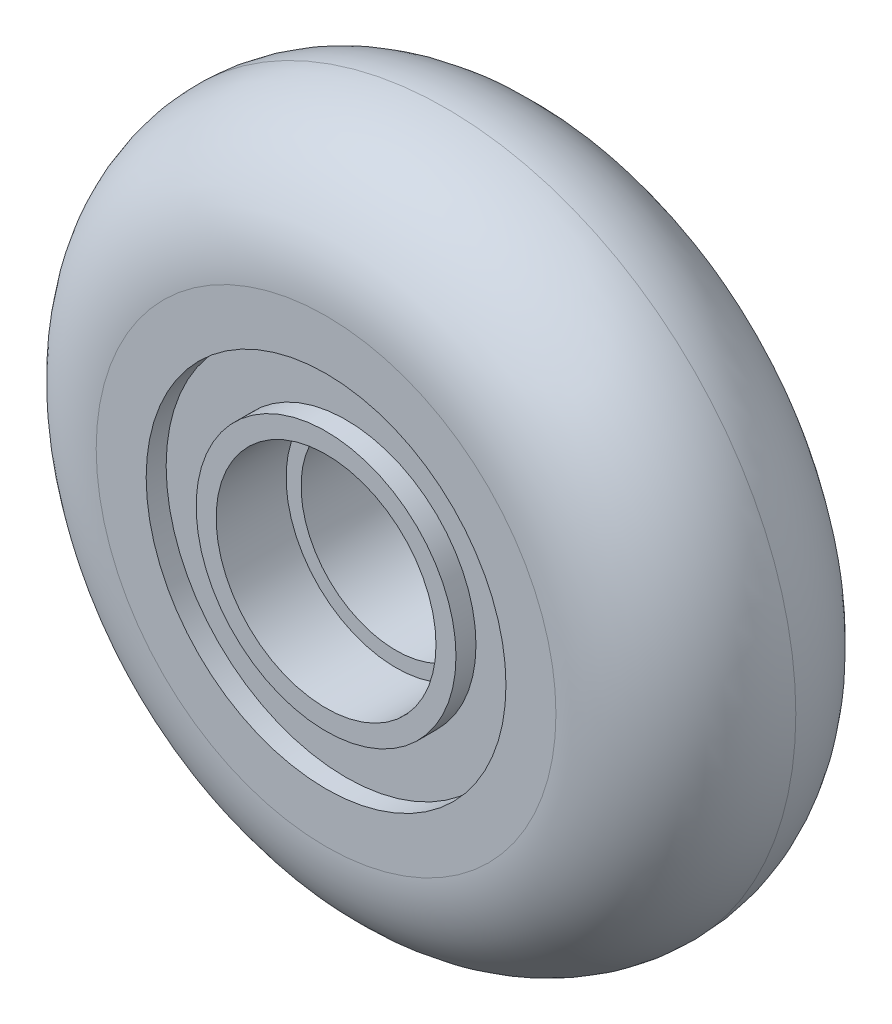
SolidWorks part; units mm, degrees
ref_plane "Face" through (0, 0, 0) normal (0, 0, 1) x (1, 0, 0)
ref_plane "Dessus" through (0, 0, 0) normal (0, 1, 0) x (1, 0, 0)
ref_plane "Droite" through (0, 0, 0) normal (1, 0, 0) x (0, 0, -1)
sketch "Esquisse1" plane through (0, 0, 0) normal (0, 0, 1) x (1, 0, 0)
  circle A0 centre (0, 0) radius 35
  dimension "D1" = 70
extrude "Extrusion1" add sketch "Esquisse1" along normal blind 24
fillet "Congé1" radius 12 1 edges at (35, 0, 24)
fillet "Congé2" radius 12 1 edges at (35, 0, 0)
sketch "Esquisse2" plane through (0, 0, 24) normal (0, 0, 1) x (1, 0, 0)
  circle A0 centre (0, 0) radius 11
  dimension "D1" = 22
extrude "Enlèv. mat.-Extru.1" cut sketch "Esquisse2" against normal blind 7
sketch "Esquisse3" plane through (0, 0, 0) normal (0, 0, -1) x (-1, 0, 0)
  circle A0 centre (0, 0) radius 11
  dimension "D1" = 22
extrude "Enlèv. mat.-Extru.2" cut sketch "Esquisse3" against normal blind 7
sketch "Esquisse5" plane through (0, 0, 17) normal (0, 0, 1) x (1, 0, 0)
  circle A0 centre (0, 0) radius 9.5
  dimension "D1" = 19
extrude "Enlèv. mat.-Extru.3" cut sketch "Esquisse5" against normal through all
sketch "Esquisse6" plane through (0, 0, 17) normal (0, 0, 1) x (1, 0, 0)
  line L0 (0, 0) -> (0, 11) construction
  line L1 (0, 0) -> (9.5263, -5.5) construction
  line L2 (0, 0) -> (-9.5263, -5.5) construction
  circle A0 centre (0, 0) radius 11 construction
  circle A1 centre (0, 0) radius 11 construction
  dimension "D1" = 120
  dimension "D2" = 120
sketch "Esquisse8" plane through (0, 0, 0) normal (0, 0, -1) x (-1, 0, 0)
  circle A0 centre (0, 0) radius 13
  circle A1 centre (0, 0) radius 18
  dimension "D1" = 26
  dimension "D2" = 36
extrude "Enlèv. mat.-Extru.4" cut sketch "Esquisse8" against normal blind 2 contours A1 | A0
sketch "Esquisse9" plane through (0, 0, 24) normal (0, 0, 1) x (1, 0, 0)
  circle A0 centre (0, 0) radius 13
  circle A1 centre (0, 0) radius 18
  dimension "D1" = 26
  dimension "D2" = 36
extrude "Enlèv. mat.-Extru.5" cut sketch "Esquisse9" against normal blind 2
